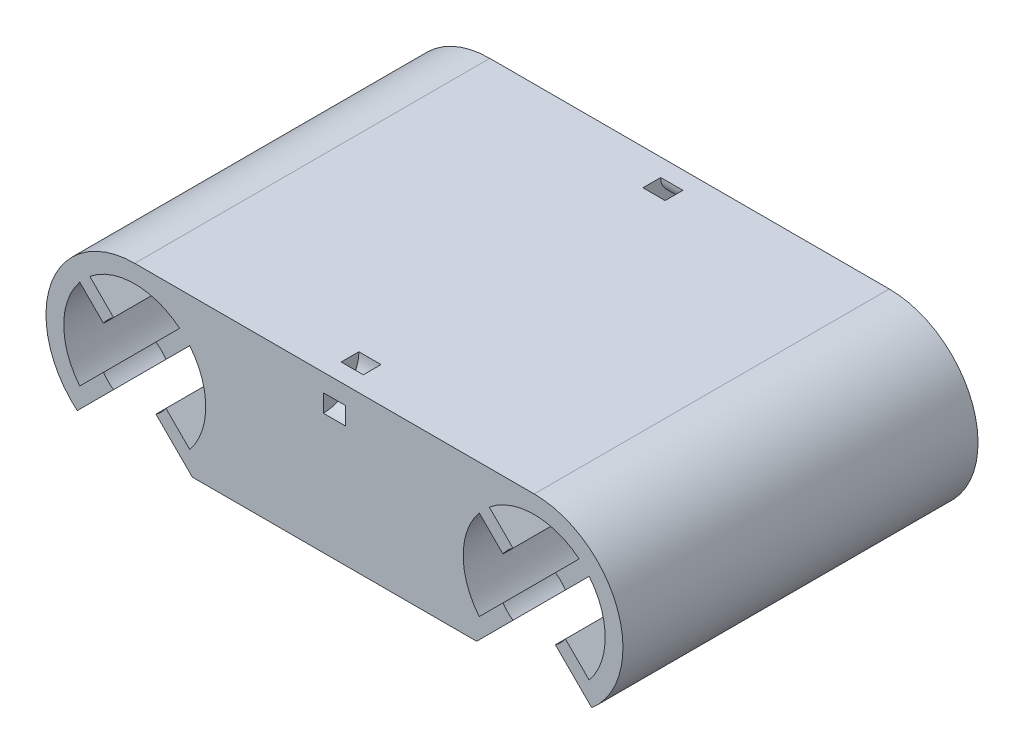
SolidWorks part; units mm, degrees
material "ABS"
ref_plane "Front Plane" through (0, 0, 0) normal (0, 0, 1) x (1, 0, 0)
ref_plane "Top Plane" through (0, 0, 0) normal (0, 1, 0) x (1, 0, 0)
ref_plane "Right Plane" through (0, 0, 0) normal (1, 0, 0) x (0, 0, -1)
sketch "Sketch1" plane through (0, 0, 0) normal (0, 0, 1) x (1, 0, 0)
  line L0 (-18.9828, 2.3858) -> (-16.3058, 5.0628)
  line L1 (-16.0173, -7.6141) -> (16.0173, -7.6141)
  line L2 (-20.1142, 3.5172) -> (-17.4372, 6.1942)
  line L3 (-24.8858, 3.5172) -> (-27.5628, 6.1942)
  line L4 (-26.0172, 2.3858) -> (-28.6942, 5.0628)
  line L5 (-26.0172, -2.3858) -> (-28.6942, -5.0628)
  line L6 (24.8858, 3.5172) -> (27.5628, 6.1942)
  line L7 (20.1142, -3.5172) -> (16.0173, -7.6141)
  line L8 (20.1142, 3.5172) -> (17.4372, 6.1942)
  line L9 (26.0172, 2.3858) -> (28.6942, 5.0628)
  line L10 (18.9828, -2.3858) -> (16.3058, -5.0628)
  line L11 (26.0172, -2.3858) -> (28.6942, -5.0628)
  line L12 (18.9828, 2.3858) -> (16.3058, 5.0628)
  line L13 (24.8858, -3.5172) -> (28.9827, -7.6141)
  line L14 (-24.8858, -3.5172) -> (-28.9827, -7.6141)
  line L15 (-20.1142, -3.5172) -> (-16.0173, -7.6141)
  line L16 (-18.9828, -2.3858) -> (-16.3058, -5.0628)
  line L17 (-22.5, 10) -> (22.5, 10)
  arc A0 (-26.0172, -2.3858) -> (-24.8858, -3.5172) centre (-22.5, 0) ccw
  arc A1 (-22.5, 10) -> (-28.9827, -7.6141) centre (-22.5, 0) ccw
  arc A2 (-28.6942, 5.0628) -> (-28.6942, -5.0628) centre (-22.5, 0) ccw
  arc A3 (-24.8858, 3.5172) -> (-26.0172, 2.3858) centre (-22.5, 0) ccw
  arc A4 (-18.9828, 2.3858) -> (-20.1142, 3.5172) centre (-22.5, 0) ccw
  arc A5 (-20.1142, -3.5172) -> (-18.9828, -2.3858) centre (-22.5, 0) ccw
  arc A6 (26.0172, 2.3858) -> (24.8858, 3.5172) centre (22.5, 0) ccw
  arc A7 (-17.4372, 6.1942) -> (-27.5628, 6.1942) centre (-22.5, 0) ccw
  arc A8 (16.3058, 5.0628) -> (16.3058, -5.0628) centre (22.5, 0) ccw
  arc A10 (28.9827, -7.6141) -> (22.5, 10) centre (22.5, 0) ccw
  arc A11 (28.6942, -5.0628) -> (28.6942, 5.0628) centre (22.5, 0) ccw
  arc A12 (20.1142, 3.5172) -> (18.9828, 2.3858) centre (22.5, 0) ccw
  arc A13 (24.8858, -3.5172) -> (26.0172, -2.3858) centre (22.5, 0) ccw
  arc A14 (18.9828, -2.3858) -> (20.1142, -3.5172) centre (22.5, 0) ccw
  arc A15 (27.5628, 6.1942) -> (17.4372, 6.1942) centre (22.5, 0) ccw
  arc A16 (-16.3058, -5.0628) -> (-16.3058, 5.0628) centre (-22.5, 0) ccw
extrude "Boss-Extrude1" add sketch "Sketch1" along normal blind 40
sketch "Sketch2" plane through (0, 0, 0) normal (1, 0, 0) x (0, 0, -1)
  line L0 (-40, 6) -> (-40, 8)
  line L1 (-38, 10) -> (-36, 10)
  line L4 (-2, 10) -> (-4, 10)
  line L5 (0, 6) -> (0, 8)
  arc A0 (-40, 8) -> (-38, 10) centre (-40, 10) ccw
  arc A1 (-40, 6) -> (-36, 10) centre (-40, 10) ccw
  arc A2 (0, 6) -> (-4, 10) centre (0, 10) cw
  arc A3 (0, 8) -> (-2, 10) centre (0, 10) cw
extrude "Cut-Extrude1" cut sketch "Sketch2" against normal blind 1.25 and the other way blind 1.25
